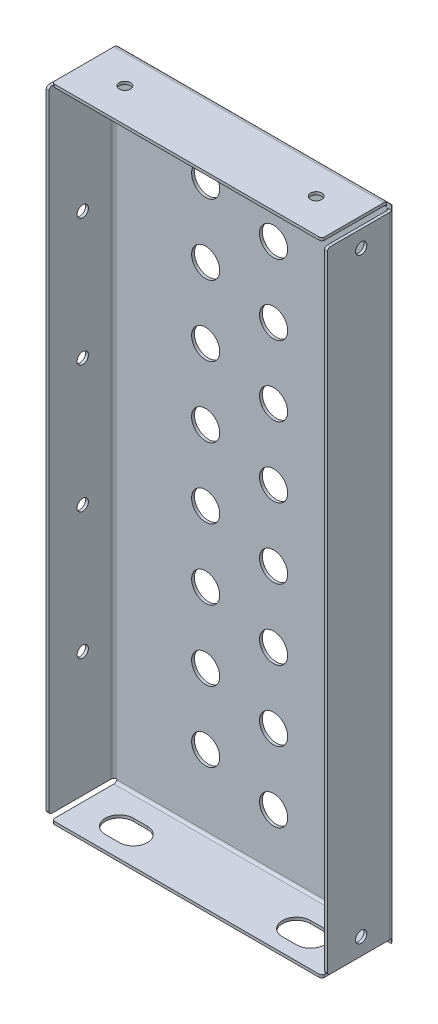
SolidWorks part; units mm, degrees
ref_plane "Спереди" through (0, 0, 0) normal (0, 0, 1) x (1, 0, 0)
ref_plane "Сверху" through (0, 0, 0) normal (0, 1, 0) x (1, 0, 0)
ref_plane "Справа" through (0, 0, 0) normal (1, 0, 0) x (0, 0, -1)
sketch "Эскиз1" plane through (0, 0, 0) normal (0, 0, 1) x (1, 0, 0)
  line L0 (0, 0) -> (0, 228)
  line L1 (0, 228) -> (100, 228)
  line L2 (100, 228) -> (100, 0)
  line L3 (100, 0) -> (0, 0)
  dimension "D1" = 228
  dimension "D2" = 100
extrude "Бобышка-Вытянуть1" add sketch "Эскиз1" along normal blind 1
sketch "Эскиз2" plane through (0, 0, 1) normal (0, 0, 1) x (1, 0, 0)
  line L2 (98, 227) -> (2, 227)
  line L4 (0, 0) -> (100, 0)
  line L5 (100, 0) -> (100, 228)
  line L6 (100, 228) -> (0, 228)
  line L7 (0, 228) -> (0, 0)
  line L8 (2, 0) -> (98, 0)
  line L9 (100, 2) -> (100, 226)
  line L10 (98, 228) -> (2, 228)
  line L11 (0, 226) -> (0, 2)
  line L12 (1, 227) -> (1, 1) construction
  line L13 (99, 227) -> (1, 227) construction
  line L14 (0, 228) -> (0, 0) construction
  line L15 (100, 228) -> (0, 228) construction
  line L16 (99, 1) -> (99, 227) construction
  line L17 (100, 0) -> (100, 228) construction
  line L18 (1, 1) -> (99, 1) construction
  line L19 (0, 0) -> (100, 0) construction
  line L20 (2, 1) -> (98, 1)
  line L21 (100, 0) -> (100, 228) construction
  line L22 (2, 0) -> (2, 1)
  line L23 (0, 2) -> (1, 2)
  line L25 (98, 1) -> (98, 0)
  line L26 (100, 2) -> (99, 2)
  line L27 (99, 2) -> (99, 226)
  line L28 (98, 228) -> (98, 227)
  line L29 (99, 226) -> (100, 226)
  line L30 (0, 226) -> (1, 226)
  line L31 (2, 227) -> (2, 228)
  line L32 (1, 226) -> (1, 2)
  dimension "D3" = 2
  dimension "D4" = 2
  dimension "D5" = 1
  dimension "D1" = 0
  dimension "D2" = 1
extrude "Бобышка-Вытянуть2" add sketch "Эскиз2" along normal blind 23
fillet "Скругление1" radius 0.9 4 edges at (50, 1, 1) (99, 114, 1) (1, 114, 1) (50, 227, 1)
fillet "Скругление2" radius 1.9 4 edges at (50, 228, 0) (100, 114, 0) (50, 0, 0) (0, 114, 0)
sketch "Эскиз3" plane through (0, 0, 1) normal (0, 0, 1) x (1, 0, 0)
  line L1 (0.2267, 226) -> (0.2267, 227.7733)
  line L2 (0.2267, 227.7733) -> (2, 227.7733)
  line L9 (0.2267, 226) -> (1.6709, 226)
  line L17 (118, 226.3291) -> (118, 227.7733)
  line L18 (119.7733, 226) -> (118.3291, 226)
  line L19 (119.7733, 227.7733) -> (118, 227.7733)
  line L20 (119.7733, 226) -> (119.7733, 227.7733)
  line L22 (2, 226.3291) -> (2, 227.7733)
  line L23 (2, 1.6709) -> (2, 0.2267)
  line L24 (119.7733, 2) -> (119.7733, 0.2267)
  line L25 (119.7733, 0.2267) -> (118, 0.2267)
  line L26 (119.7733, 2) -> (118.3291, 2)
  line L27 (118, 1.6709) -> (118, 0.2267)
  line L28 (0.2267, 2) -> (1.6709, 2)
  line L29 (0.2267, 0.2267) -> (2, 0.2267)
  line L30 (0.2267, 2) -> (0.2267, 0.2267)
  arc A4 (1.6709, 226) -> (2, 226.3291) centre (1.9, 226.1) ccw
  arc A5 (118.3291, 226) -> (118, 226.3291) centre (118.1, 226.1) cw
  arc A6 (118.3291, 2) -> (118, 1.6709) centre (118.1, 1.9) ccw
  arc A7 (1.6709, 2) -> (2, 1.6709) centre (1.9, 1.9) cw
extrude "Вырез-Вытянуть1" cut sketch "Эскиз3" against normal blind 22 and the other way blind 22
fillet "Скругление3" radius 1 8 edges at (98, 227.5, 24) (99.5, 226, 24) (0.5, 226, 24) (2, 227.5, 24) (0.5, 2, 24) (2, 0.5, 24) (98, 0.5, 24) (99.5, 2, 24)
sketch "Эскиз4" plane through (0, 0, 1) normal (0, 0, 1) x (1, 0, 0)
  circle A1 centre (33.7037, 202) radius 5
  circle A2 centre (33.7037, 177) radius 5
  circle A3 centre (33.7037, 152) radius 5
  circle A4 centre (33.7037, 127) radius 5
  circle A5 centre (33.7037, 102) radius 5
  circle A6 centre (33.7037, 77) radius 5
  circle A7 centre (33.7037, 52) radius 5
  circle A8 centre (33.7037, 27) radius 5
  circle A9 centre (57.8519, 20.5295) radius 5
  circle A10 centre (57.8519, 45.5295) radius 5
  circle A11 centre (57.8519, 70.5295) radius 5
  circle A12 centre (57.8519, 95.5295) radius 5
  circle A13 centre (57.8519, 120.5295) radius 5
  circle A14 centre (57.8519, 145.5295) radius 5
  circle A15 centre (57.8519, 170.5295) radius 5
  circle A16 centre (57.8519, 195.5295) radius 5
  circle A17 centre (82, 202) radius 5
  circle A18 centre (82, 177) radius 5
  circle A19 centre (82, 152) radius 5
  circle A20 centre (82, 127) radius 5
  circle A21 centre (82, 102) radius 5
  circle A22 centre (82, 77) radius 5
  circle A23 centre (82, 52) radius 5
  circle A24 centre (82, 27) radius 5
extrude "Вырез-Вытянуть2" cut sketch "Эскиз4" against normal blind 10
sketch "Эскиз5" plane through (0, 228, 0) normal (0, 1, 0) x (1, 0, 0)
  circle A0 centre (16, -12) radius 2
  circle A1 centre (84, -12) radius 2
  circle A2 centre (84, 252) radius 2
  circle A3 centre (16, 252) radius 2
extrude "Вырез-Вытянуть3" cut sketch "Эскиз5" against normal blind 30
sketch "Эскиз6" plane through (100, 0, 0) normal (1, 0, 0) x (0, 0, -1)
  circle A0 centre (-12, 220) radius 2 construction
  circle A1 centre (-12, 220) radius 2
extrude "Вырез-Вытянуть4" cut sketch "Эскиз6" against normal blind 30
sketch "Эскиз7" plane through (100, 0, 0) normal (1, 0, 0) x (0, 0, -1)
  circle A0 centre (-12, 8) radius 2 construction
  circle A1 centre (-12, 8) radius 2
extrude "Вырез-Вытянуть5" cut sketch "Эскиз7" against normal blind 30
sketch "Эскиз8" plane through (0, 0, 0) normal (-1, 0, 0) x (0, 0, 1)
  circle A0 centre (12, 181.9) radius 2 construction
  circle A1 centre (12, 181.9) radius 2
  circle A2 centre (12, 46.3) radius 2 construction
  circle A3 centre (12, 91.5) radius 2 construction
  circle A4 centre (12, 136.7) radius 2 construction
  circle A5 centre (12, 46.3) radius 2
  circle A6 centre (12, 91.5) radius 2
  circle A7 centre (12, 136.7) radius 2
extrude "Вырез-Вытянуть6" cut sketch "Эскиз8" against normal blind 30
sketch "Эскиз9" plane through (0, 1, 0) normal (0, 1, 0) x (1, 0, 0)
  line L0 (1, -23) -> (1, -1.9) construction
  line L1 (16, -9) -> (21, -9)
  line L2 (16, -19) -> (21, -19)
  line L3 (97, -24) -> (3, -24) construction
  line L4 (50, -24) -> (50, -1.9) construction
  line L5 (98, -1.9) -> (2, -1.9) construction
  line L6 (84, -19) -> (79, -19)
  line L7 (84, -9) -> (79, -9)
  line L8 (16, -14) -> (17, -14)
  arc A2 (16, -9) -> (16, -19) centre (16, -14) ccw
  arc A3 (21, -19) -> (21, -9) centre (21, -14) ccw
  arc A4 (79, -19) -> (79, -9) centre (79, -14) cw
  arc A5 (84, -9) -> (84, -19) centre (84, -14) cw
  dimension "D1" = 5
  dimension "D2" = 5
  dimension "D3" = 15
  dimension "D4" = 10
extrude "Вырез-Вытянуть7" cut sketch "Эскиз9" against normal blind 10 contours L2 A3 L1 A2 | A5 L7 A4 L6 region at (18.5, 1, 14) region at (81.5, 1, 14)
